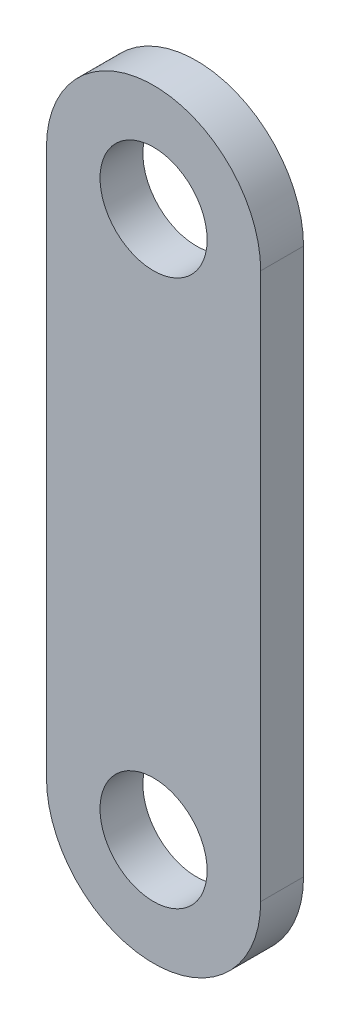
SolidWorks part; units mm, degrees
ref_plane "前基準面" through (0, 0, 0) normal (0, 0, 1) x (1, 0, 0)
ref_plane "上基準面" through (0, 0, 0) normal (0, 1, 0) x (1, 0, 0)
ref_plane "右基準面" through (0, 0, 0) normal (1, 0, 0) x (0, 0, -1)
ref_plane "平面1"
sketch "草圖1" plane through (0, 0, 0) normal (0, 0, 1) x (1, 0, 0)
  line L0 (50, 255) -> (50, 0)
  line L1 (-50, 0) -> (-50, 255)
  arc A0 (50, 255) -> (-50, 255) centre (0, 255) ccw
  arc A1 (-50, 0) -> (50, 0) centre (0, 0) ccw
  circle A2 centre (0, 0) radius 25
  circle A3 centre (0, 255) radius 25
  dimension "D1" = 50
  dimension "D2" = 100
  dimension "D4" = 50
  dimension "D5" = 100
  dimension "D3" = 255
extrude "擠出1" add sketch "草圖1" along normal blind 10 and the other way blind 10 contours L1 A1 L0 A0 A3 A2 region at (0, 127.5, 0)
